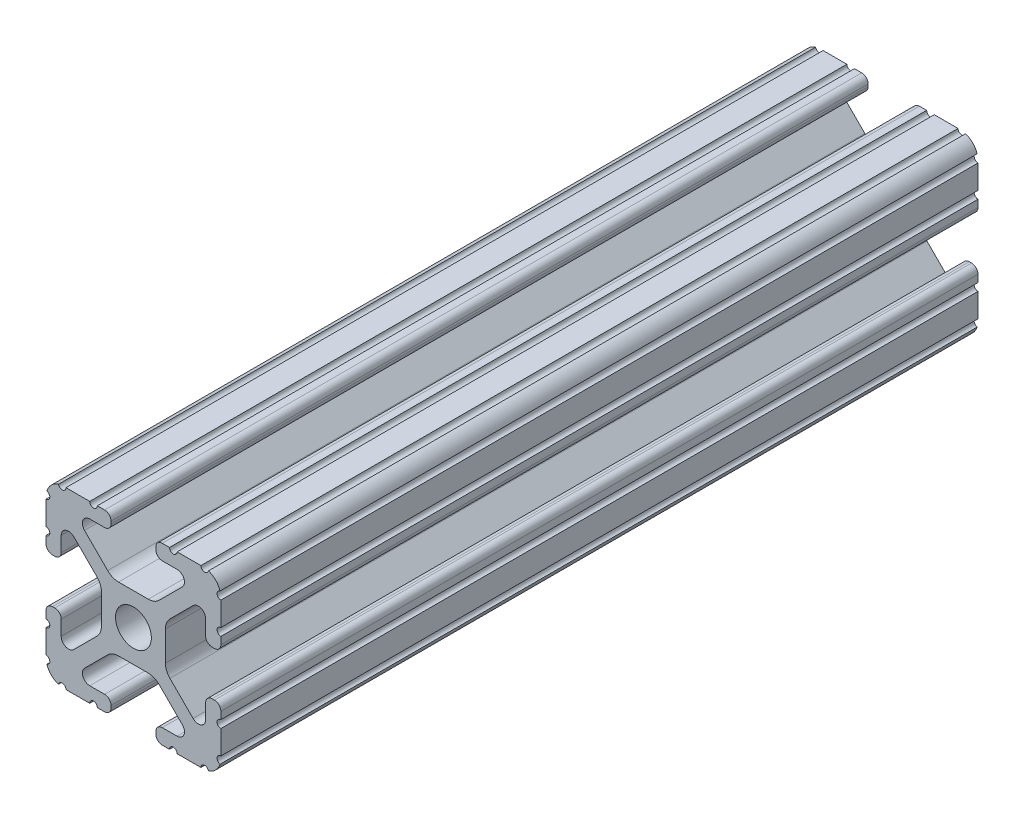
SolidWorks part; units mm, degrees
ref_plane "Front Plane" through (0, 0, 0) normal (0, 0, 1) x (1, 0, 0)
ref_plane "Top Plane" through (0, 0, 0) normal (0, 1, 0) x (1, 0, 0)
ref_plane "Right Plane" through (0, 0, 0) normal (1, 0, 0) x (0, 0, -1)
sketch "Sketch2" plane through (0, 0, 0) normal (0, 0, 1) x (1, 0, 0)
  line L0 (0, 12.7) -> (0, -12.7) construction
  line L1 (-12.7, 0) -> (12.7, 0) construction
  line L2 (3.2512, -12.7) -> (12.7, -12.7)
  line L3 (12.7, -12.7) -> (12.7, -3.2512)
  line L4 (3.2512, -12.7) -> (3.2512, -10.4902)
  line L5 (3.2512, -10.4902) -> (8.9276, -10.4902)
  line L6 (8.9276, -10.4902) -> (3.0856, -4.6482)
  line L7 (0, 0) -> (12.7, -12.7) construction
  line L8 (12.7, -3.2512) -> (10.4902, -3.2512)
  line L9 (10.4902, -3.2512) -> (10.4902, -8.9276)
  line L10 (10.4902, -8.9276) -> (4.6482, -3.0856)
  circle A0 centre (0, 0) radius 2.6035
  arc A1 (6.3485, -10.4902) -> (7.1039, -8.6665) centre (6.3485, -9.4219) ccw construction
  point P8 (0, -4.6482)
  dimension "Center Hole Diameter" = 5.207
  dimension "Rail Height" = 25.4
  dimension "Rail Width" = 25.4
  dimension "T-Slot Width" = 6.5024
  dimension "Slot Inner Width" = 14.8336
  dimension "Thickness" = 2.2098
  dimension "Slot Depth" = 5.842
  dimension "D1" = 2.2098
sketch "Sketch3" plane through (0, 0, 0) normal (1, 0, 0) x (0, 0, -1)
  line L0 (-76.2, -12.7) -> (76.2, -12.7) construction
  line L1 (-68.58, 0) -> (68.58, 0) construction
  dimension "Length" = 152.4
  dimension "D1" = 137.16
sketch "Sketch4" plane through (0, 0, 0) normal (0, 0, 1) x (1, 0, 0)
  line L0 (4.1904, -12.7) -> (10.1173, -12.7)
  line L1 (3.2512, -12.7) -> (12.7, -12.7) construction
  line L2 (3.2512, -12.7) -> (3.2512, -10.4902) construction
  line L3 (3.2512, -10.4902) -> (8.9276, -10.4902) construction
  line L4 (3.2512, -11.4294) -> (3.2512, -11.7608)
  line L5 (4.1904, -10.4902) -> (6.3485, -10.4902)
  line L6 (0, -4.6482) -> (2.164, -4.6482)
  line L7 (8.9276, -10.4902) -> (3.0856, -4.6482) construction
  line L8 (3.7373, -5.2999) -> (7.1039, -8.6665)
  line L9 (12.7, -12.7) -> (12.7, -3.2512) construction
  line L10 (10.4902, -8.9276) -> (4.6482, -3.0856) construction
  line L11 (10.4902, -3.2512) -> (10.4902, -8.9276) construction
  line L12 (10.4902, -6.3485) -> (10.4902, -4.1904)
  line L13 (12.7, -3.2512) -> (10.4902, -3.2512) construction
  line L14 (11.4294, -3.2512) -> (11.7608, -3.2512)
  line L15 (12.7, -4.1904) -> (12.7, -10.1173)
  line L16 (8.6665, -7.1039) -> (5.2999, -3.7373)
  line L17 (4.6482, 0) -> (4.6482, -2.164)
  line L18 (-12.7, 0) -> (12.7, 0) construction
  line L19 (0, -4.6482) -> (0, -2.6035)
  line L20 (0, 12.7) -> (0, -12.7) construction
  line L21 (4.6482, 0) -> (2.6035, 0)
  arc A0 (3.2512, -11.7608) -> (4.1904, -12.7) centre (4.1904, -11.7608) ccw
  arc A2 (3.2512, -11.4294) -> (4.1904, -10.4902) centre (4.1904, -11.4294) cw
  arc A3 (6.3485, -10.4902) -> (7.1039, -8.6665) centre (6.3485, -9.4219) ccw
  arc A4 (2.164, -4.6482) -> (3.7373, -5.2999) centre (2.164, -6.8732) cw
  arc A5 (10.1173, -12.7) -> (12.7, -10.1173) centre (10.1173, -10.1173) ccw
  arc A6 (8.6665, -7.1039) -> (10.4902, -6.3485) centre (9.4219, -6.3485) ccw
  arc A7 (10.4902, -4.1904) -> (11.4294, -3.2512) centre (11.4294, -4.1904) cw
  arc A8 (11.7608, -3.2512) -> (12.7, -4.1904) centre (11.7608, -4.1904) cw
  arc A9 (5.2999, -3.7373) -> (4.6482, -2.164) centre (6.8732, -2.164) cw
  circle A10 centre (0, 0) radius 2.6035 construction
  arc A11 (0, -2.6035) -> (2.6035, 0) centre (0, 0) ccw
  dimension "D1" = 2.5827
  dimension "D2" = 2.225
  dimension "D3" = 0.9392
extrude "Boss-Extrude1" add sketch "Sketch4" along normal mid plane 152.4
sketch "Sketch5" plane through (0, 0, 0) normal (0, 0, 1) x (1, 0, 0)
  line L0 (3.2512, -12.7) -> (12.7, -12.7) construction
  line L1 (4.1904, -10.4902) -> (6.3485, -10.4902) construction
  line L3 (0, 0) -> (12.7, -12.7) construction
  line L4 (6.3485, -10.4902) -> (6.3485, -12.7) construction
  line L5 (8.9276, -10.4902) -> (3.0856, -4.6482) construction
  circle A0 centre (10.3562, -12.7) radius 0.5524
  circle A1 centre (5.796, -12.7) radius 0.5524
  circle A2 centre (12.7, -10.3562) radius 0.5524
  circle A3 centre (12.7, -5.796) radius 0.5524
  point P10 (5.2694, -10.4902)
  point P12 (9.4219, -6.3485)
  dimension "D1" = 1.1049
extrude "Cut-Extrude1" cut sketch "Sketch5" against normal through all both and the other way through all
mirror "Mirror1" about plane through (0, 0, 0) normal (1, 0, 0) of bodies 137 134
mirror "Mirror2" about plane through (0, 0, 0) normal (0, 1, 0) of bodies 135
sketch "Sketch6" plane through (0, 0, 76.2) normal (0, 0, 1) x (1, 0, 0)
  line L44 (12.7, -5.2436) -> (12.7, -4.1904)
  line L45 (11.7608, -3.2512) -> (11.4294, -3.2512)
  line L46 (10.4902, -4.1904) -> (10.4902, -6.3485)
  line L47 (8.6665, -7.1039) -> (5.2999, -3.7373)
  line L48 (4.6482, -2.164) -> (4.6482, 2.164)
  line L49 (5.2999, 3.7373) -> (8.6665, 7.1039)
  line L50 (10.4902, 6.3485) -> (10.4902, 4.1904)
  line L51 (11.4294, 3.2512) -> (11.7608, 3.2512)
  line L52 (12.7, 4.1904) -> (12.7, 5.2436)
  line L53 (12.7, 6.3485) -> (12.7, 9.8037)
  line L54 (9.8037, 12.7) -> (6.3485, 12.7)
  line L55 (5.2436, 12.7) -> (4.1904, 12.7)
  line L56 (3.2512, 11.7608) -> (3.2512, 11.4294)
  line L57 (4.1904, 10.4902) -> (6.3485, 10.4902)
  line L58 (7.1039, 8.6665) -> (3.7373, 5.2999)
  line L59 (2.164, 4.6482) -> (-2.164, 4.6482)
  line L60 (-3.7373, 5.2999) -> (-7.1039, 8.6665)
  line L61 (-6.3485, 10.4902) -> (-4.1904, 10.4902)
  line L62 (-3.2512, 11.4294) -> (-3.2512, 11.7608)
  line L63 (-4.1904, 12.7) -> (-5.2436, 12.7)
  line L64 (-6.3485, 12.7) -> (-9.8037, 12.7)
  line L65 (-12.7, 9.8037) -> (-12.7, 6.3485)
  line L66 (-12.7, 5.2436) -> (-12.7, 4.1904)
  line L67 (-11.7608, 3.2512) -> (-11.4294, 3.2512)
  line L68 (-10.4902, 4.1904) -> (-10.4902, 6.3485)
  line L69 (-8.6665, 7.1039) -> (-5.2999, 3.7373)
  line L70 (-4.6482, 2.164) -> (-4.6482, -2.164)
  line L71 (-5.2999, -3.7373) -> (-8.6665, -7.1039)
  line L72 (-10.4902, -6.3485) -> (-10.4902, -4.1904)
  line L73 (-11.4294, -3.2512) -> (-11.7608, -3.2512)
  line L74 (-12.7, -4.1904) -> (-12.7, -5.2436)
  line L75 (-12.7, -6.3485) -> (-12.7, -9.8037)
  line L76 (-9.8037, -12.7) -> (-6.3485, -12.7)
  line L77 (-5.2436, -12.7) -> (-4.1904, -12.7)
  line L78 (-3.2512, -11.7608) -> (-3.2512, -11.4294)
  line L79 (-4.1904, -10.4902) -> (-6.3485, -10.4902)
  line L80 (-7.1039, -8.6665) -> (-3.7373, -5.2999)
  line L81 (-2.164, -4.6482) -> (2.164, -4.6482)
  line L82 (3.7373, -5.2999) -> (7.1039, -8.6665)
  line L83 (6.3485, -10.4902) -> (4.1904, -10.4902)
  line L84 (3.2512, -11.4294) -> (3.2512, -11.7608)
  line L85 (4.1904, -12.7) -> (5.2436, -12.7)
  line L86 (6.3485, -12.7) -> (9.8037, -12.7)
  line L87 (12.7, -9.8037) -> (12.7, -6.3485)
  line L88 (12.7, -5.2436) -> (12.7, -4.1904)
  line L89 (11.7608, -3.2512) -> (11.4294, -3.2512)
  line L90 (10.4902, -4.1904) -> (10.4902, -6.3485)
  line L91 (8.6665, -7.1039) -> (5.2999, -3.7373)
  line L92 (4.6482, -2.164) -> (4.6482, 2.164)
  line L93 (5.2999, 3.7373) -> (8.6665, 7.1039)
  line L94 (10.4902, 6.3485) -> (10.4902, 4.1904)
  line L95 (11.4294, 3.2512) -> (11.7608, 3.2512)
  line L96 (12.7, 4.1904) -> (12.7, 5.2436)
  line L97 (12.7, 6.3485) -> (12.7, 9.8037)
  line L98 (9.8037, 12.7) -> (6.3485, 12.7)
  line L99 (5.2436, 12.7) -> (4.1904, 12.7)
  line L100 (3.2512, 11.7608) -> (3.2512, 11.4294)
  line L101 (4.1904, 10.4902) -> (6.3485, 10.4902)
  line L102 (7.1039, 8.6665) -> (3.7373, 5.2999)
  line L103 (2.164, 4.6482) -> (-2.164, 4.6482)
  line L104 (-3.7373, 5.2999) -> (-7.1039, 8.6665)
  line L105 (-6.3485, 10.4902) -> (-4.1904, 10.4902)
  line L106 (-3.2512, 11.4294) -> (-3.2512, 11.7608)
  line L107 (-4.1904, 12.7) -> (-5.2436, 12.7)
  line L108 (-6.3485, 12.7) -> (-9.8037, 12.7)
  line L109 (-12.7, 9.8037) -> (-12.7, 6.3485)
  line L110 (-12.7, 5.2436) -> (-12.7, 4.1904)
  line L111 (-11.7608, 3.2512) -> (-11.4294, 3.2512)
  line L112 (-10.4902, 4.1904) -> (-10.4902, 6.3485)
  line L113 (-8.6665, 7.1039) -> (-5.2999, 3.7373)
  line L114 (-4.6482, 2.164) -> (-4.6482, -2.164)
  line L115 (-5.2999, -3.7373) -> (-8.6665, -7.1039)
  line L116 (-10.4902, -6.3485) -> (-10.4902, -4.1904)
  line L117 (-11.4294, -3.2512) -> (-11.7608, -3.2512)
  line L118 (-12.7, -4.1904) -> (-12.7, -5.2436)
  line L119 (-12.7, -6.3485) -> (-12.7, -9.8037)
  line L120 (-9.8037, -12.7) -> (-6.3485, -12.7)
  line L121 (-5.2436, -12.7) -> (-4.1904, -12.7)
  line L122 (-3.2512, -11.7608) -> (-3.2512, -11.4294)
  line L123 (-4.1904, -10.4902) -> (-6.3485, -10.4902)
  line L124 (-7.1039, -8.6665) -> (-3.7373, -5.2999)
  line L125 (-2.164, -4.6482) -> (2.164, -4.6482)
  line L126 (3.7373, -5.2999) -> (7.1039, -8.6665)
  line L127 (6.3485, -10.4902) -> (4.1904, -10.4902)
  line L128 (3.2512, -11.4294) -> (3.2512, -11.7608)
  line L129 (4.1904, -12.7) -> (5.2436, -12.7)
  line L130 (6.3485, -12.7) -> (9.8037, -12.7)
  line L131 (12.7, -9.8037) -> (12.7, -6.3485)
  circle A0 centre (0, 0) radius 2.6035
  arc A52 (12.7, -5.2436) -> (12.7, -6.3485) centre (12.7, -5.796) ccw
  arc A53 (12.7, -4.1904) -> (11.7608, -3.2512) centre (11.7608, -4.1904) ccw
  arc A54 (11.4294, -3.2512) -> (10.4902, -4.1904) centre (11.4294, -4.1904) ccw
  arc A55 (8.6665, -7.1039) -> (10.4902, -6.3485) centre (9.4219, -6.3485) ccw
  arc A56 (4.6482, -2.164) -> (5.2999, -3.7373) centre (6.8732, -2.164) ccw
  arc A57 (5.2999, 3.7373) -> (4.6482, 2.164) centre (6.8732, 2.164) ccw
  arc A58 (10.4902, 6.3485) -> (8.6665, 7.1039) centre (9.4219, 6.3485) ccw
  arc A59 (10.4902, 4.1904) -> (11.4294, 3.2512) centre (11.4294, 4.1904) ccw
  arc A60 (11.7608, 3.2512) -> (12.7, 4.1904) centre (11.7608, 4.1904) ccw
  arc A61 (12.7, 6.3485) -> (12.7, 5.2436) centre (12.7, 5.796) ccw
  arc A62 (12.58, 10.8954) -> (12.7, 9.8037) centre (12.7, 10.3562) ccw
  arc A63 (12.58, 10.8954) -> (10.8954, 12.58) centre (10.1173, 10.1173) ccw
  arc A64 (9.8037, 12.7) -> (10.8954, 12.58) centre (10.3562, 12.7) ccw
  arc A65 (5.2436, 12.7) -> (6.3485, 12.7) centre (5.796, 12.7) ccw
  arc A66 (4.1904, 12.7) -> (3.2512, 11.7608) centre (4.1904, 11.7608) ccw
  arc A67 (3.2512, 11.4294) -> (4.1904, 10.4902) centre (4.1904, 11.4294) ccw
  arc A68 (7.1039, 8.6665) -> (6.3485, 10.4902) centre (6.3485, 9.4219) ccw
  arc A69 (2.164, 4.6482) -> (3.7373, 5.2999) centre (2.164, 6.8732) ccw
  arc A70 (-3.7373, 5.2999) -> (-2.164, 4.6482) centre (-2.164, 6.8732) ccw
  arc A71 (-6.3485, 10.4902) -> (-7.1039, 8.6665) centre (-6.3485, 9.4219) ccw
  arc A72 (-4.1904, 10.4902) -> (-3.2512, 11.4294) centre (-4.1904, 11.4294) ccw
  arc A73 (-3.2512, 11.7608) -> (-4.1904, 12.7) centre (-4.1904, 11.7608) ccw
  arc A74 (-6.3485, 12.7) -> (-5.2436, 12.7) centre (-5.796, 12.7) ccw
  arc A75 (-10.8954, 12.58) -> (-9.8037, 12.7) centre (-10.3562, 12.7) ccw
  arc A76 (-10.8954, 12.58) -> (-12.58, 10.8954) centre (-10.1173, 10.1173) ccw
  arc A77 (-12.7, 9.8037) -> (-12.58, 10.8954) centre (-12.7, 10.3562) ccw
  arc A78 (-12.7, 5.2436) -> (-12.7, 6.3485) centre (-12.7, 5.796) ccw
  arc A79 (-12.7, 4.1904) -> (-11.7608, 3.2512) centre (-11.7608, 4.1904) ccw
  arc A80 (-11.4294, 3.2512) -> (-10.4902, 4.1904) centre (-11.4294, 4.1904) ccw
  arc A81 (-8.6665, 7.1039) -> (-10.4902, 6.3485) centre (-9.4219, 6.3485) ccw
  arc A82 (-4.6482, 2.164) -> (-5.2999, 3.7373) centre (-6.8732, 2.164) ccw
  arc A83 (-5.2999, -3.7373) -> (-4.6482, -2.164) centre (-6.8732, -2.164) ccw
  arc A84 (-10.4902, -6.3485) -> (-8.6665, -7.1039) centre (-9.4219, -6.3485) ccw
  arc A85 (-10.4902, -4.1904) -> (-11.4294, -3.2512) centre (-11.4294, -4.1904) ccw
  arc A86 (-11.7608, -3.2512) -> (-12.7, -4.1904) centre (-11.7608, -4.1904) ccw
  arc A87 (-12.7, -6.3485) -> (-12.7, -5.2436) centre (-12.7, -5.796) ccw
  arc A88 (-12.58, -10.8954) -> (-12.7, -9.8037) centre (-12.7, -10.3562) ccw
  arc A89 (-12.58, -10.8954) -> (-10.8954, -12.58) centre (-10.1173, -10.1173) ccw
  arc A90 (-9.8037, -12.7) -> (-10.8954, -12.58) centre (-10.3562, -12.7) ccw
  arc A91 (-5.2436, -12.7) -> (-6.3485, -12.7) centre (-5.796, -12.7) ccw
  arc A92 (-4.1904, -12.7) -> (-3.2512, -11.7608) centre (-4.1904, -11.7608) ccw
  arc A93 (-3.2512, -11.4294) -> (-4.1904, -10.4902) centre (-4.1904, -11.4294) ccw
  arc A94 (-7.1039, -8.6665) -> (-6.3485, -10.4902) centre (-6.3485, -9.4219) ccw
  arc A95 (-2.164, -4.6482) -> (-3.7373, -5.2999) centre (-2.164, -6.8732) ccw
  arc A96 (3.7373, -5.2999) -> (2.164, -4.6482) centre (2.164, -6.8732) ccw
  arc A97 (6.3485, -10.4902) -> (7.1039, -8.6665) centre (6.3485, -9.4219) ccw
  arc A98 (4.1904, -10.4902) -> (3.2512, -11.4294) centre (4.1904, -11.4294) ccw
  arc A99 (3.2512, -11.7608) -> (4.1904, -12.7) centre (4.1904, -11.7608) ccw
  arc A100 (6.3485, -12.7) -> (5.2436, -12.7) centre (5.796, -12.7) ccw
  arc A101 (10.8954, -12.58) -> (9.8037, -12.7) centre (10.3562, -12.7) ccw
  arc A102 (10.8954, -12.58) -> (12.58, -10.8954) centre (10.1173, -10.1173) ccw
  arc A103 (12.7, -9.8037) -> (12.58, -10.8954) centre (12.7, -10.3562) ccw
  arc A104 (12.7, -5.2436) -> (12.7, -6.3485) centre (12.7, -5.796) ccw
  arc A105 (12.7, -4.1904) -> (11.7608, -3.2512) centre (11.7608, -4.1904) ccw
  arc A106 (11.4294, -3.2512) -> (10.4902, -4.1904) centre (11.4294, -4.1904) ccw
  arc A107 (8.6665, -7.1039) -> (10.4902, -6.3485) centre (9.4219, -6.3485) ccw
  arc A108 (4.6482, -2.164) -> (5.2999, -3.7373) centre (6.8732, -2.164) ccw
  arc A109 (5.2999, 3.7373) -> (4.6482, 2.164) centre (6.8732, 2.164) ccw
  arc A110 (10.4902, 6.3485) -> (8.6665, 7.1039) centre (9.4219, 6.3485) ccw
  arc A111 (10.4902, 4.1904) -> (11.4294, 3.2512) centre (11.4294, 4.1904) ccw
  arc A112 (11.7608, 3.2512) -> (12.7, 4.1904) centre (11.7608, 4.1904) ccw
  arc A113 (12.7, 6.3485) -> (12.7, 5.2436) centre (12.7, 5.796) ccw
  arc A114 (12.58, 10.8954) -> (12.7, 9.8037) centre (12.7, 10.3562) ccw
  arc A115 (12.58, 10.8954) -> (10.8954, 12.58) centre (10.1173, 10.1173) ccw
  arc A116 (9.8037, 12.7) -> (10.8954, 12.58) centre (10.3562, 12.7) ccw
  arc A117 (5.2436, 12.7) -> (6.3485, 12.7) centre (5.796, 12.7) ccw
  arc A118 (4.1904, 12.7) -> (3.2512, 11.7608) centre (4.1904, 11.7608) ccw
  arc A119 (3.2512, 11.4294) -> (4.1904, 10.4902) centre (4.1904, 11.4294) ccw
  arc A120 (7.1039, 8.6665) -> (6.3485, 10.4902) centre (6.3485, 9.4219) ccw
  arc A121 (2.164, 4.6482) -> (3.7373, 5.2999) centre (2.164, 6.8732) ccw
  arc A122 (-3.7373, 5.2999) -> (-2.164, 4.6482) centre (-2.164, 6.8732) ccw
  arc A123 (-6.3485, 10.4902) -> (-7.1039, 8.6665) centre (-6.3485, 9.4219) ccw
  arc A124 (-4.1904, 10.4902) -> (-3.2512, 11.4294) centre (-4.1904, 11.4294) ccw
  arc A125 (-3.2512, 11.7608) -> (-4.1904, 12.7) centre (-4.1904, 11.7608) ccw
  arc A126 (-6.3485, 12.7) -> (-5.2436, 12.7) centre (-5.796, 12.7) ccw
  arc A127 (-10.8954, 12.58) -> (-9.8037, 12.7) centre (-10.3562, 12.7) ccw
  arc A128 (-10.8954, 12.58) -> (-12.58, 10.8954) centre (-10.1173, 10.1173) ccw
  arc A129 (-12.7, 9.8037) -> (-12.58, 10.8954) centre (-12.7, 10.3562) ccw
  arc A130 (-12.7, 5.2436) -> (-12.7, 6.3485) centre (-12.7, 5.796) ccw
  arc A131 (-12.7, 4.1904) -> (-11.7608, 3.2512) centre (-11.7608, 4.1904) ccw
  arc A132 (-11.4294, 3.2512) -> (-10.4902, 4.1904) centre (-11.4294, 4.1904) ccw
  arc A133 (-8.6665, 7.1039) -> (-10.4902, 6.3485) centre (-9.4219, 6.3485) ccw
  arc A134 (-4.6482, 2.164) -> (-5.2999, 3.7373) centre (-6.8732, 2.164) ccw
  arc A135 (-5.2999, -3.7373) -> (-4.6482, -2.164) centre (-6.8732, -2.164) ccw
  arc A136 (-10.4902, -6.3485) -> (-8.6665, -7.1039) centre (-9.4219, -6.3485) ccw
  arc A137 (-10.4902, -4.1904) -> (-11.4294, -3.2512) centre (-11.4294, -4.1904) ccw
  arc A138 (-11.7608, -3.2512) -> (-12.7, -4.1904) centre (-11.7608, -4.1904) ccw
  arc A139 (-12.7, -6.3485) -> (-12.7, -5.2436) centre (-12.7, -5.796) ccw
  arc A140 (-12.58, -10.8954) -> (-12.7, -9.8037) centre (-12.7, -10.3562) ccw
  arc A141 (-12.58, -10.8954) -> (-10.8954, -12.58) centre (-10.1173, -10.1173) ccw
  arc A142 (-9.8037, -12.7) -> (-10.8954, -12.58) centre (-10.3562, -12.7) ccw
  arc A143 (-5.2436, -12.7) -> (-6.3485, -12.7) centre (-5.796, -12.7) ccw
  arc A144 (-4.1904, -12.7) -> (-3.2512, -11.7608) centre (-4.1904, -11.7608) ccw
  arc A145 (-3.2512, -11.4294) -> (-4.1904, -10.4902) centre (-4.1904, -11.4294) ccw
  arc A146 (-7.1039, -8.6665) -> (-6.3485, -10.4902) centre (-6.3485, -9.4219) ccw
  arc A147 (-2.164, -4.6482) -> (-3.7373, -5.2999) centre (-2.164, -6.8732) ccw
  arc A148 (3.7373, -5.2999) -> (2.164, -4.6482) centre (2.164, -6.8732) ccw
  arc A149 (6.3485, -10.4902) -> (7.1039, -8.6665) centre (6.3485, -9.4219) ccw
  arc A150 (4.1904, -10.4902) -> (3.2512, -11.4294) centre (4.1904, -11.4294) ccw
  arc A151 (3.2512, -11.7608) -> (4.1904, -12.7) centre (4.1904, -11.7608) ccw
  arc A152 (6.3485, -12.7) -> (5.2436, -12.7) centre (5.796, -12.7) ccw
  arc A153 (10.8954, -12.58) -> (9.8037, -12.7) centre (10.3562, -12.7) ccw
  arc A154 (10.8954, -12.58) -> (12.58, -10.8954) centre (10.1173, -10.1173) ccw
  arc A155 (12.7, -9.8037) -> (12.58, -10.8954) centre (12.7, -10.3562) ccw
  dimension "D1" = 0
extrude "Cut-Extrude3" cut sketch "Sketch6" against normal blind 42.418
equation "\"D1@Boss-Extrude1\"=\"Length@Sketch3\""
equation "\"D1@Sketch2\"=\"Thickness@Sketch2\""
equation "\"D2@Sketch4\"=\"Slot Inner Width@Sketch2\"*0.15"
equation "\"D1@Sketch4\"=\"D3@Sketch4\"*2.75"
equation "\"D3@Sketch4\"=\"Thickness@Sketch2\"*0.425"
equation "\"D1@Sketch5\"=\"Thickness@Sketch2\"*0.5"
equation "\"D1@Sketch3\"=\"Length@Sketch3\"*0.9"
